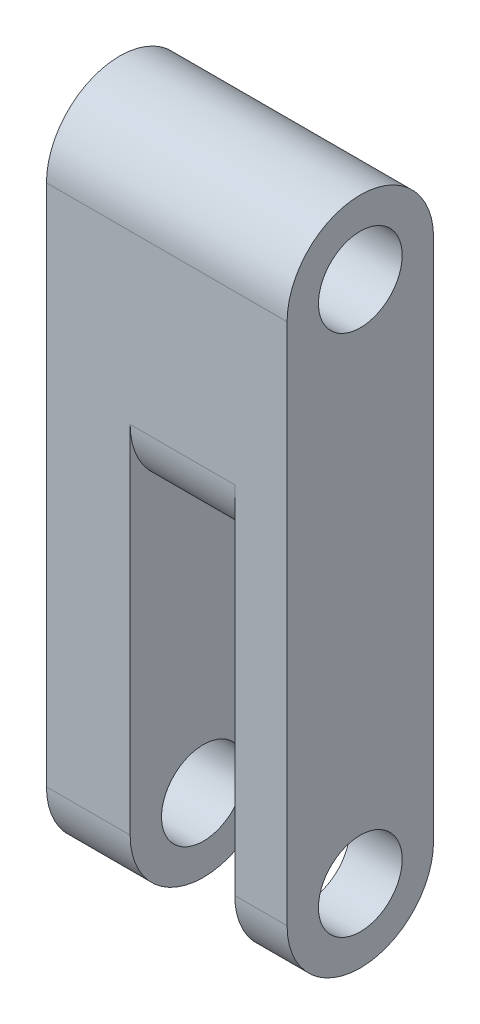
SolidWorks part; units mm, degrees
material "ABS"
ref_plane "Спереди" through (0, 0, 0) normal (0, 0, 1) x (1, 0, 0)
ref_plane "Сверху" through (0, 0, 0) normal (0, 1, 0) x (1, 0, 0)
ref_plane "Справа" through (0, 0, 0) normal (1, 0, 0) x (0, 0, -1)
sketch "Эскиз1" plane through (0, 0, 0) normal (1, 0, 0) x (0, 0, -1)
  line L0 (3.5, 30) -> (3.5, -49970) construction
  line L2 (0, 0) -> (0, 25)
  line L4 (7, 0) -> (7, 25)
  line L5 (0, 0) -> (7, 25) construction
  line L6 (0, 25) -> (7, 0) construction
  line L7 (3.5, 12.5) -> (50003.5, 12.5) construction
  circle A0 centre (3.5, 25) radius 2
  arc A1 (0, 25) -> (7, 25) centre (3.5, 25) cw
  circle A2 centre (3.5, 0) radius 2
  arc A3 (0, 0) -> (7, 0) centre (3.5, 0) ccw
  point P4 (3.5, 12.5)
  dimension "D3" = 4
  dimension "D4" = 3.5
  dimension "D1" = 25
  dimension "D2" = 7
  dimension "D5" = 25
extrude "Бобышка-Вытянуть1" add sketch "Эскиз1" along normal blind 11.5 contours L2 A1 L4 A3
sketch "Эскиз2" plane through (11.5, 0, 0) normal (1, 0, 0) x (0, 0, -1)
  line L0 (0, 11.9718) -> (0, 50011.9718) construction
  line L2 (7, 19.5747) -> (7, -49980.4253) construction
  line L4 (3.5, 33.5) -> (3.5, -49966.5) construction
  line L5 (0, 0) -> (50000, 0) construction
  line L6 (0, 25) -> (50000, 25) construction
  line L7 (-2.9994, 12.5) -> (49997.0006, 12.5) construction
  arc A0 (7, 25) -> (0, 25) centre (3.5, 25) ccw construction
  arc A1 (0, 0) -> (7, 0) centre (3.5, 0) ccw construction
  circle A2 centre (3.5, 25) radius 2
  circle A3 centre (3.5, 0) radius 2
  point P9 (3.5, 28.5)
  point P13 (3.5, -3.5)
  point P22 (3.5, 25)
  dimension "D3" = 4
  dimension "D1" = 25
  dimension "D2" = 12.5
extrude "Вырез-Вытянуть2" cut sketch "Эскиз2" against normal blind 15
ref_plane "Плоскость1" through (4, 0, 0) normal (1, 0, 0) x (0, 0, -1)
sketch "Эскиз3" plane through (4, 0, 0) normal (1, 0, 0) x (0, 0, -1)
  line L0 (0, 0) -> (50000, 0) construction
  line L1 (-996.5, 25) -> (49003.5, 25) construction
  line L3 (-1005.198, 17) -> (48994.802, 17) construction
  line L4 (-14.8525, 21) -> (12.3896, 21) construction
  line L8 (-5.9735, 17) -> (-5.9735, -6.2075)
  line L9 (-5.9735, -6.2075) -> (11.9268, -6.2075)
  line L10 (11.9268, -6.2075) -> (11.9268, 17)
  line L12 (7, 17) -> (11.9268, 17)
  line L13 (0, 17) -> (-5.9735, 17)
  arc A3 (0, 17) -> (7, 17) centre (3.5, 17) ccw
  dimension "D4" = 23.2075
  dimension "D5" = 17.9003
  dimension "D3" = 3.5
  dimension "D1" = 8
  dimension "D2" = 4
  dimension "D6" = 8.4268
extrude "Вырез-Вытянуть3" cut sketch "Эскиз3" along normal blind 5
